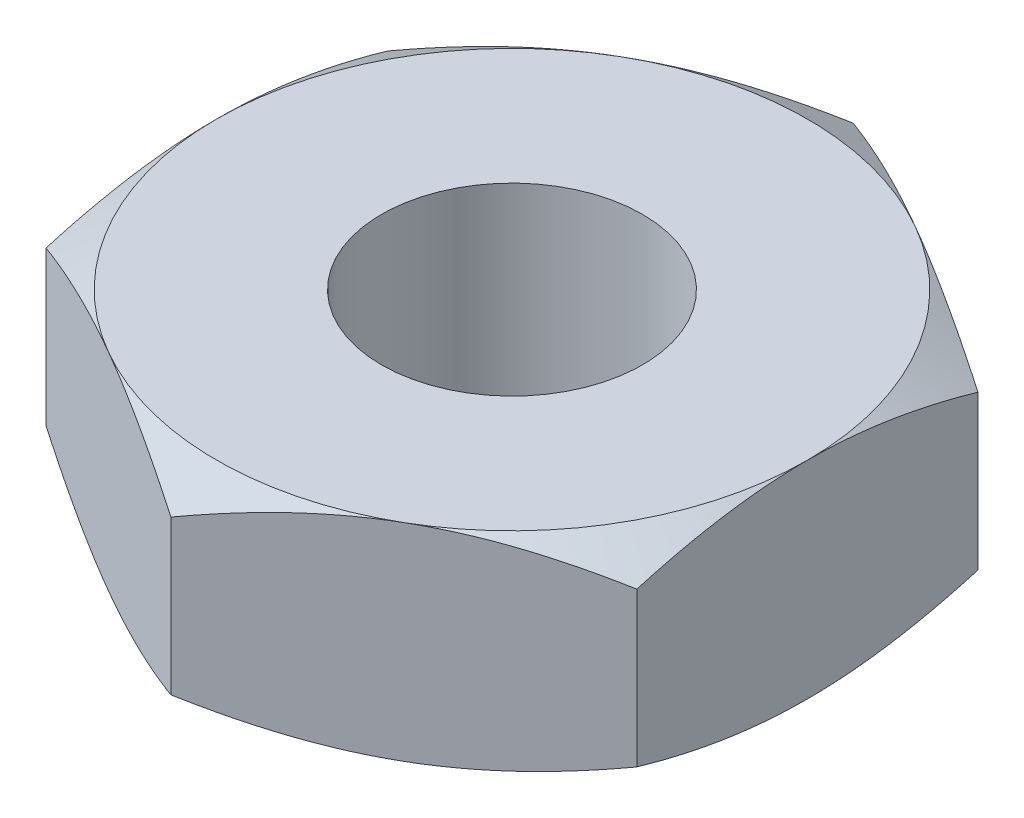
SolidWorks part; units mm, degrees
material "6061-T6 (SS)"
ref_plane "Front Plane" through (0, 0, 0) normal (0, 0, 1) x (1, 0, 0)
ref_plane "Top Plane" through (0, 0, 0) normal (0, 1, 0) x (1, 0, 0)
ref_plane "Right Plane" through (0, 0, 0) normal (1, 0, 0) x (0, 0, -1)
sketch "Sketch7" plane through (0, 0, 0) normal (0, 1, 0) x (1, 0, 0)
  line L0 (-3.9688, 0) -> (3.9688, 0) construction
  line L1 (-1.7526, 0) -> (1.7526, 0) construction
  line L2 (-3.9688, 0) -> (-3.9688, -0.7937) construction
  point P4 (0, 0)
  point P8 (0, 0)
sketch "Sketch6" plane through (0, 0, 0) normal (1, 0, 0) x (0, 0, -1)
  line L0 (0, 1.3891) -> (0, -1.3891) construction
  point P4 (0, 0)
sketch "Sketch1" plane through (0, 0, 0) normal (0, 1, 0) x (1, 0, 0)
  line L1 (-3.9688, 2.2914) -> (-3.9688, -2.2914)
  line L2 (-3.9688, -2.2914) -> (0, -4.5827)
  line L3 (0, -4.5827) -> (3.9688, -2.2914)
  line L4 (3.9688, -2.2914) -> (3.9687, 2.2914)
  line L5 (3.9687, 2.2914) -> (0, 4.5827)
  line L6 (0, 4.5827) -> (-3.9688, 2.2914)
  circle A0 centre (0, 0) radius 3.9688 construction
  circle A1 centre (0, 0) radius 1.7526
extrude "Boss-Extrude1" add sketch "Sketch1" along normal mid plane 2.7781
sketch "Sketch5" plane through (0, 1.3891, 0) normal (0, 1, 0) x (1, 0, 0)
  circle A0 centre (0, 0) radius 3.9688 construction
  circle A1 centre (0, 0) radius 3.9688
extrude "Cut-Extrude2" cut sketch "Sketch5" against normal through all draft 60 flip side to cut
mirror "Mirror1" about plane through (0, 0, 0) normal (0, 1, 0) of "Cut-Extrude2"
sketch "Sketch14" plane through (0, 1.3891, 0) normal (0, 1, 0) x (1, 0, 0)
  line L0 (-1.7526, 0) -> (1.7526, 0) construction
  line L1 (0, 1.7526) -> (0, -1.7526) construction
  circle A0 centre (0, 0) radius 1.7526 construction
  point P7 (0, 0)
  point P11 (0, 0)
  point P12 (0, -1.7526)
  point P13 (-1.7526, 0)
  point P14 (0, 1.7526)
  point P15 (1.7526, 0)
sketch "Sketch8" [suppressed] plane through (0, 1.3891, 0) normal (0, 1, 0) x (1, 0, 0)
  circle A0 centre (0, 0) radius 1.7526 construction
  circle A1 centre (0, 0) radius 1.7526
extrude "Boss-Extrude2" [suppressed] add sketch "Sketch8" against normal up to surface (2.7781 mm away) separate body
sketch "Sketch9" [suppressed] plane through (0, 1.3891, 0) normal (0, 1, 0) x (1, 0, 0)
  circle A0 centre (0, 0) radius 1.7526 construction
  circle A1 centre (0, 0) radius 1.7526
extrude "Boss-Extrude3" [suppressed] add sketch "Sketch9" against normal up to surface (2.7781 mm away)
sketch "Sketch10" [suppressed] plane through (0, 1.3891, 0) normal (0, 1, 0) x (1, 0, 0)
  circle A0 centre (0, 0) radius 1.7526 construction
  circle A1 centre (0, 0) radius 1.7526
curve "Helix/Spiral1" [suppressed] pitch 0.7937 height 3.5719 turns 4.5
sketch "Sketch11" [suppressed] plane through (0, 0, 0) normal (1, 0, 0) x (0, 0, -1)
  line L0 (-1.7526, 1.3891) -> (-1.7526, 2.0836)
  line L1 (1.7526, 1.3891) -> (-1.7526, 1.3891) construction
  line L2 (-1.7526, 2.0836) -> (-1.237, 1.7859)
  line L3 (-1.237, 1.7859) -> (-1.237, 1.6867)
  line L4 (-1.237, 1.6867) -> (-1.7526, 1.3891)
  line L5 (-1.7526, 1.7363) -> (-1.237, 1.7363) construction
  line L6 (-1.4948, 1.9348) -> (-1.4948, 1.5379) construction
  spline S0 degree 3 poles (-1.7526, 1.3891) (-1.7526, 1.3726) (-1.6613, 1.3394) (-1.2715, 1.2899) (-0.6882, 1.2402) (0, 1.1906) (0.6882, 1.141) (1.2715, 1.0914) (1.6613, 1.0418) (1.7982, 0.9922) (1.6613, 0.9426) (1.2715, 0.893) (0.6882, 0.8434) (0, 0.7938) (-0.6882, 0.7441) (-1.2715, 0.6945) (-1.6613, 0.6449) (-1.7982, 0.5953) (-1.6613, 0.5457) (-1.2715, 0.4961) (-0.6882, 0.4465) (0, 0.3969) (0.6882, 0.3473) (1.2715, 0.2977) (1.6613, 0.248) (1.7982, 0.1984) (1.6613, 0.1488) (1.2715, 0.0992) (0.6882, 0.0496) (0, 0) (-0.6882, -0.0496) (-1.2715, -0.0992) (-1.6613, -0.1488) (-1.7982, -0.1984) (-1.6613, -0.248) (-1.2715, -0.2977) (-0.6882, -0.3473) (0, -0.3969) (0.6882, -0.4465) (1.2715, -0.4961) (1.6613, -0.5457) (1.7982, -0.5953) (1.6613, -0.6449) (1.2715, -0.6945) (0.6882, -0.7441) (0, -0.7937) (-0.6882, -0.8434) (-1.2715, -0.893) (-1.6613, -0.9426) (-1.7982, -0.9922) (-1.6613, -1.0418) (-1.2715, -1.0914) (-0.6882, -1.141) (0, -1.1906) (0.6882, -1.2402) (1.2715, -1.2898) (1.6613, -1.3395) (1.7982, -1.3891) (1.6613, -1.4387) (1.2715, -1.4883) (0.6882, -1.5379) (0, -1.5875) (-0.6882, -1.6371) (-1.2715, -1.6867) (-1.6613, -1.7363) (-1.7982, -1.7859) (-1.6613, -1.8355) (-1.2715, -1.8852) (-0.6882, -1.9348) (0, -1.9844) (0.6882, -2.034) (1.2715, -2.0836) (1.6613, -2.1332) (1.7526, -2.1664) (1.7526, -2.1828) knots 0 0 0 0 0.013889 0.027778 0.041667 0.055556 0.069444 0.083333 0.097222 0.111111 0.125 0.138889 0.152778 0.166667 0.180556 0.194444 0.208333 0.222222 0.236111 0.25 0.263889 0.277778 0.291667 0.305556 0.319444 0.333333 0.347222 0.361111 0.375 0.388889 0.402778 0.416667 0.430556 0.444444 0.458333 0.472222 0.486111 0.5 0.513889 0.527778 0.541667 0.555556 0.569444 0.583333 0.597222 0.611111 0.625 0.638889 0.652778 0.666667 0.680556 0.694444 0.708333 0.722222 0.736111 0.75 0.763889 0.777778 0.791667 0.805556 0.819444 0.833333 0.847222 0.861111 0.875 0.888889 0.902778 0.916667 0.930556 0.944444 0.958333 0.972222 0.986111 1 1 1 1 construction
  dimension "D1" = 60
  dimension "D2" = 0.0992
  dimension "D3" = 0.3969
sweep "Cut-Sweep1" [suppressed] cut profiles "Sketch11" path "Helix/Spiral1"
combine bodies "Combine1" [suppressed] operation type subtract main body 107 bodies to subtract 108
sketch "Sketch12" [suppressed] plane through (0, 1.3891, 0) normal (0, 1, 0) x (1, 0, 0)
  circle A1 centre (0, 0) radius 1.7526
  circle A2 centre (0, 0) radius 1.7526
  dimension "D1" = 0
extrude "Cut-Extrude3" [suppressed] cut sketch "Sketch12" against normal through all draft 45
sketch "Sketch13" [suppressed] plane through (0, -1.3891, 0) normal (0, -1, 0) x (1, 0, 0)
  circle A1 centre (0, 0) radius 1.7526
  circle A2 centre (0, 0) radius 1.7526
  dimension "D1" = 0
extrude "Cut-Extrude4" [suppressed] cut sketch "Sketch13" against normal through all draft 45
equation "\"D3@Helix/Spiral1\"=\"Thickness@Sketch6\"+\"Pitch@Sketch7\""
equation "\"Height@Boss-Extrude1\"=\"Thickness@Sketch6\""
equation "\"D4@Helix/Spiral1\"=\"Pitch@Sketch7\""
equation "\"D2@Sketch11\"=\"Pitch@Sketch7\"*.125"
equation "\"D3@Sketch11\"=\"Pitch@Sketch7\"*.5"
